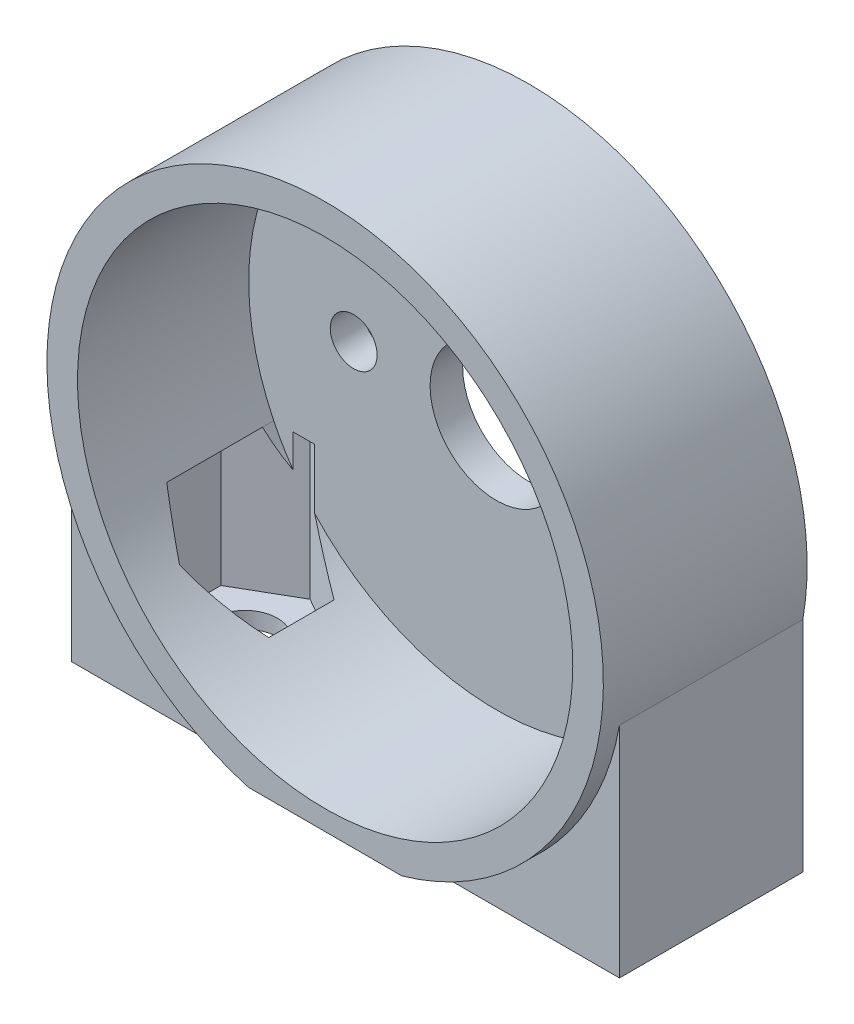
SolidWorks part; units mm, degrees
ref_plane "Front Plane" through (0, 0, 0) normal (0, 0, 1) x (1, 0, 0)
ref_plane "Top Plane" through (0, 0, 0) normal (0, 1, 0) x (1, 0, 0)
ref_plane "Right Plane" through (0, 0, 0) normal (1, 0, 0) x (0, 0, -1)
sketch "Sketch1" plane through (0, 0, 0) normal (0, 0, 1) x (1, 0, 0)
  circle A0 centre (0, 0) radius 12.15
  circle A1 centre (0, 0) radius 13.65
extrude "Boss-Extrude1" add sketch "Sketch1" along normal blind 10
sketch "Sketch2" plane through (0, 0, 10) normal (0, 0, 1) x (1, 0, 0)
  line L0 (5.5, 0) -> (-5.5, 0) construction
  line L1 (-9.25, 0) -> (9.25, 0) construction
  line L2 (0, -5.5) -> (0, 5.5) construction
  circle A0 centre (0, 0) radius 13.65
  circle A1 centre (0, 0) radius 4.25
  circle A2 centre (9.25, 0) radius 1.5
  circle A3 centre (-9.25, 0) radius 1.5
  point P10 (0, 0)
  point P13 (0, 0)
  dimension "D1" = 18.5
  dimension "D2" = 8.5
  dimension "D3" = 3
sketch "Sketch3" plane through (0, 0, 0) normal (0, 0, -1) x (-1, 0, 0)
  line L0 (-9.44, -13.65) -> (9.44, -13.65) construction
  line L2 (0, 5.5) -> (0, -5.5) construction
  line L4 (-13.44, -2.3851) -> (-13.44, -13.65)
  line L5 (-13.44, -13.65) -> (13.44, -13.65)
  line L6 (13.44, -2.3851) -> (13.44, -13.65)
  circle A1 centre (0, 0) radius 13.65 construction
  circle A3 centre (0, 0) radius 13.65
  point P2 (0, -13.65)
  point P13 (0, -13.65)
  circle M5 centre (0, 0) radius 13.65
  dimension "D1" = 18.88
  dimension "D2" = 4
extrude "Boss-Extrude3" add sketch "Sketch3" against normal blind 9 contours L4 L5 M5 | L5 L6 M5 region at (10.4018, -10.8034, 0) region at (-10.4018, -10.8034, 0)
sketch "Sketch5" plane through (0, -13.65, 0) normal (0, -1, 0) x (1, 0, 0)
  line L0 (-13.65, 10) -> (-13.65, 0) construction
  line L1 (-9.44, 4.5) -> (9.44, 4.5) construction
  line L2 (-9.44, 0) -> (-9.44, 9) construction
  line L3 (15.015, 0) -> (-15.015, 0) construction
  line L4 (0, 9) -> (-13.44, 9) construction
  line L5 (0, -5.5) -> (0, 5.5) construction
  circle A0 centre (-9.44, 4.5) radius 1.6
  circle A2 centre (9.44, 4.5) radius 1.6
  point P4 (0, 4.5)
  point P14 (-9.44, 4.5)
  dimension "D1" = 18.88
  dimension "D3" = 3.2
extrude "Cut-Extrude1" cut sketch "Sketch5" against normal blind 7
sketch "Sketch6" plane through (0, 0, 0) normal (0, 0, -1) x (-1, 0, 0)
  line L1 (-13.44, -13.65) -> (13.44, -13.65)
  line L2 (-13.44, -13.65) -> (-13.44, -13.12)
  line L3 (-13.44, -13.12) -> (13.44, -13.12)
  line L4 (13.44, -13.65) -> (13.44, -13.12)
  line L6 (13.44, -2.3851) -> (13.44, -13.65) construction
  dimension "D1" = 0.53
extrude "Cut-Extrude2" cut sketch "Sketch6" against normal through all
sketch "Sketch7" plane through (0, 0, 0) normal (0, 0, -1) x (-1, 0, 0)
  line L0 (9.25, 0) -> (-9.25, 0) construction
  line L1 (-7, 0) -> (7, 0) construction
  line L2 (0, 5.5) -> (0, -5.5) construction
  circle A0 centre (0, 0) radius 12.15
  circle A1 centre (-7, 0) radius 1.15
  circle A2 centre (7, 0) radius 1.15
  circle A3 centre (0, 0) radius 3.25
  point P6 (0, 0)
  dimension "D1" = 14
  dimension "D2" = 2.3
  dimension "D3" = 2.3
  dimension "D4" = 6.5
extrude "Boss-Extrude4" add sketch "Sketch7" against normal blind 1.6
sketch "Sketch8" plane through (0, -13.12, 0) normal (0, -1, 0) x (1, 0, 0)
  line L0 (-13.44, 9) -> (-13.44, 0) construction
  line L1 (-12.215, 2.8979) -> (-9.44, 1.2957)
  line L2 (-9.44, 1.2957) -> (-6.665, 2.8979)
  line L3 (-6.665, 2.8979) -> (-6.665, 6.1021)
  line L4 (-6.665, 6.1021) -> (-9.44, 7.7043)
  line L5 (-9.44, 7.7043) -> (-12.215, 6.1021)
  line L6 (-12.215, 6.1021) -> (-12.215, 2.8979)
  line L7 (0, -5.5) -> (0, 5.5) construction
  line L8 (12.215, 6.1021) -> (12.215, 2.8979)
  line L9 (9.44, 7.7043) -> (12.215, 6.1021)
  line L10 (6.665, 6.1021) -> (9.44, 7.7043)
  line L11 (6.665, 2.8979) -> (6.665, 6.1021)
  line L12 (9.44, 1.2957) -> (6.665, 2.8979)
  line L13 (12.215, 2.8979) -> (9.44, 1.2957)
  line L14 (-13.44, 9) -> (-13.44, 0) construction
  circle A0 centre (-9.44, 4.5) radius 2.775 construction
  dimension "D1" = 5.55
extrude "Cut-Extrude4" cut sketch "Sketch8" against normal blind 7 from offset 0.8 offset against normal yes
